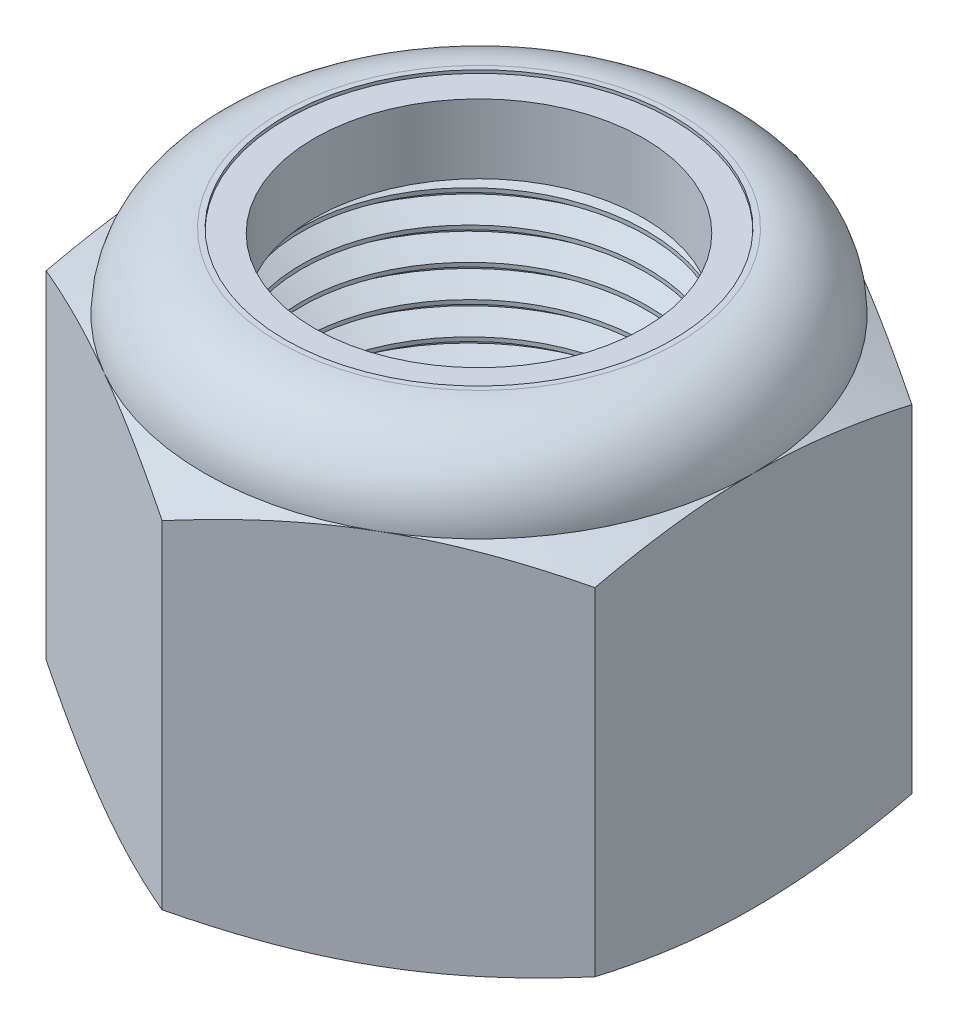
SolidWorks part; units mm, degrees
note: '?' marks a value the reader was unsure of.
ref_plane "Front" through (0, 0, 0) normal (0, 0, 1) x (1, 0, 0)
ref_plane "Top" through (0, 0, 0) normal (0, 1, 0) x (1, 0, 0)
ref_plane "Right" through (0, 0, 0) normal (1, 0, 0) x (0, 0, -1)
sketch "Sketch8" plane through (0, 0, 0) normal (1, 0, 0) x (0, 0, -1)
  line L0 (0, 0) -> (0, 22.225) construction
  line L1 (13.4937, 0) -> (-13.4937, 0) construction
  line L2 (-9.525, 22.225) -> (9.525, 22.225) construction
  line L3 (9.525, 22.225) -> (9.525, 20.6375) construction
sketch "Sketch1" plane through (0, 0, 0) normal (0, 1, 0) x (1, 0, 0)
  line L1 (0, 15.5812) -> (-13.4937, 7.7906)
  line L2 (-13.4937, 7.7906) -> (-13.4937, -7.7906)
  line L3 (-13.4937, -7.7906) -> (0, -15.5812)
  line L4 (0, -15.5812) -> (13.4938, -7.7906)
  line L5 (13.4938, -7.7906) -> (13.4938, 7.7906)
  line L6 (13.4938, 7.7906) -> (0, 15.5812)
  circle A0 centre (0, 0) radius 13.4938 construction
  circle A1 centre (0, 0) radius 9.525
extrude "Extrude1" add sketch "Sketch1" along normal up to vertex (22.225 mm away) up to point (0, 22.225, 0)
sketch "Sketch5" plane through (0, 0, 0) normal (1, 0, 0) x (0, 0, -1)
  line L0 (0, 0) -> (13.4937, 0)
  line L1 (13.4937, 0) -> (15.5812, 0.9734)
  line L2 (15.5812, 0.9734) -> (15.5812, 17.5474)
  line L3 (15.5812, 17.5474) -> (13.4937, 18.5208)
  line L4 (9.7896, 22.225) -> (9.7896, 23.495)
  line L5 (9.7896, 23.495) -> (16.8512, 23.495)
  line L6 (16.8512, 23.495) -> (16.8512, -1.27)
  line L7 (16.8512, -1.27) -> (0, -1.27)
  line L8 (0, -1.27) -> (0, 0)
  line L9 (13.4937, 18.5208) -> (13.4937, 0) construction
  line L12 (15.5812, 22.225) -> (15.5812, 0) construction
  line L13 (15.5812, 11.1125) -> (16.8512, 11.1125) construction
  line L15 (0, 0) -> (0, 23.495) construction
  line L18 (13.4937, 0) -> (-13.4937, 0) construction
  line L19 (7.7906, 22.225) -> (15.5812, 22.225) construction
  line L20 (0, 23.495) -> (9.7896, 23.495) construction
  line L21 (7.7906, 0) -> (15.5812, 0) construction
  arc A0 (13.4937, 18.5208) -> (9.7896, 22.225) centre (9.7896, 18.5208) ccw
  dimension "D1" = 25
  dimension "D2" = 1.27
  dimension "D4" = 3.7042
revolve "Cut-Revolve3" cut sketch "Sketch5" angle 360 about L15
sketch "Sketch4" plane through (0, 0, 0) normal (1, 0, 0) x (0, 0, -1)
  line L0 (0, 18.5208) -> (10.4775, 18.5208)
  line L1 (10.4775, 18.5208) -> (0, 13.6351)
  line L3 (0, 4.8857) -> (10.4775, 0)
  line L4 (10.4775, 0) -> (0, 0)
  line L5 (0, 0) -> (0, 18.5208) construction
  line L10 (0, 0) -> (0, 22.225) construction
  line L11 (0, 4.8857) -> (0, 0)
  line L12 (0, 18.5208) -> (0, 13.6351)
  line L13 (11.6859, 18.5208) -> (0, 18.5208) construction
  dimension "D1" = 25
  dimension "D2" = 20.955
sketch "Sketch6" plane through (0, 0, 0) normal (1, 0, 0) x (0, 0, -1)
  line L0 (0, 18.5208) -> (13.3414, 18.5208)
  line L1 (9.7896, 22.0726) -> (4.8948, 22.0726)
  line L2 (0, 23.495) -> (0, 18.5208)
  line L3 (4.8948, 23.495) -> (0, 23.495)
  line L4 (0, 23.495) -> (9.7896, 23.495) construction
  line L5 (0, 0) -> (0, 23.495) construction
  line L6 (0, 23.495) -> (0, 0) construction
  line L7 (4.8948, 22.0726) -> (4.8948, 23.495)
  line L8 (9.7896, 22.225) -> (9.7896, 22.0726) construction
  line L9 (4.8948, 22.0726) -> (0, 22.0726) construction
  line L10 (0, 22.0726) -> (0, 13.6351) construction
  arc A0 (13.3414, 18.5208) -> (9.7896, 22.0726) centre (9.7896, 18.5208) ccw
  arc A1 (13.4937, 18.5208) -> (9.7896, 22.225) centre (9.7896, 18.5208) ccw construction
  dimension "D1" = 0.1524
revolve "Cut-Revolve4" cut sketch "Sketch6" angle 360 about L6
revolve "Cut-Revolve2" cut sketch "Sketch4" angle 360 about L5
sketch "Sketch7" plane through (0, 0, 0) normal (1, 0, 0) x (0, 0, -1)
  line L0 (8.0962, 18.597) -> (13.2643, 18.597)
  line L1 (9.7896, 21.9964) -> (8.0962, 21.9964)
  line L2 (8.0962, 21.9964) -> (8.0962, 18.597)
  line L3 (8.0962, 18.597) -> (0, 18.597) construction
  line L4 (0, 18.597) -> (0, 21.9964) construction
  line L5 (0, 21.9964) -> (8.0962, 21.9964) construction
  line L6 (8.0962, 18.597) -> (8.0962, 18.5208) construction
  line L7 (0, 18.5208) -> (13.3414, 18.5208) construction
  line L8 (9.7896, 21.9964) -> (9.7896, 22.0726) construction
  arc A0 (13.2643, 18.597) -> (9.7896, 21.9964) centre (9.7896, 18.5208) ccw
  arc A2 (13.3414, 18.5208) -> (9.7896, 22.0726) centre (9.7896, 18.5208) ccw construction
  dimension "D1" = 0.0762
  dimension "D2" = 16.1925
revolve "Revolve2" add sketch "Sketch7" angle 360 about L4
sketch "Sketch2" plane through (0, 0, 0) normal (1, 0, 0) x (0, 0, -1)
  line L0 (-9.525, 0) -> (-9.525, 18.5208) construction
  line L1 (0, 0) -> (9.525, 0)
  line L2 (0, 0) -> (0, 18.5208)
  line L3 (0, 18.5208) -> (9.525, 18.5208)
  line L4 (9.525, 0) -> (9.525, 18.5208)
  line L6 (11.6859, 18.5208) -> (13.4937, 18.5208) construction
  line L7 (0, -9.525) -> (0, 0) construction
revolve "Revolve1" add sketch "Sketch2" angle 360 about L7
sketch "Sketch9" plane through (0, 0, 0) normal (1, 0, 0) x (0, 0, -1)
  line L0 (9.6969, 20.0091) -> (9.6969, 18.4216) construction
  line L1 (9.6969, 18.4216) -> (8.322, 19.2154) construction
  line L2 (8.322, 19.2154) -> (9.6969, 20.0091) construction
  line L3 (8.4939, 19.3146) -> (8.4939, 19.1161) construction
  line L4 (9.525, 19.9099) -> (9.525, 18.5208) construction
  line L5 (8.322, 19.2154) -> (8.4939, 19.2154) construction
  line L6 (9.525, 19.2154) -> (9.6969, 19.2154) construction
  line L7 (9.6109, 19.2154) -> (9.6109, 19.9595) construction
  line L8 (9.6969, 18.4216) -> (9.6109, 19.9595)
  line L9 (9.6109, 19.9595) -> (8.4939, 19.3146)
  line L10 (8.4939, 19.3146) -> (8.4939, 19.1161)
  line L11 (8.4939, 19.1161) -> (9.6969, 18.4216)
  dimension "D1" = 1.5875
  dimension "D2" = 0.1984
sketch "Sketch10" plane through (0, 18.5208, 0) normal (0, 1, 0) x (1, 0, 0)
  circle A1 centre (0, 0) radius 9.525
  circle A2 centre (0, 0) radius 9.525
  dimension "D1" = 0
curve "Helix/Spiral1" pitch 1.5875 height 23.8125 turns 15
sweep "Cut-Sweep1" cut profiles "Sketch9" path "Helix/Spiral1" align with end faces yes
sketch "Sketch11" plane through (0, 0, 0) normal (1, 0, 0) x (0, 0, -1)
  line L0 (0, 0) -> (0, 22.225) construction
  line L1 (13.4937, 0) -> (-13.4937, 0) construction
  line L4 (0, 22.225) -> (0, 0) construction
  line L5 (0, 11.1125) -> (9.525, 11.1125) construction
  line L6 (0, 0) -> (10.4775, 0)
  line L7 (0, 4.8857) -> (0, 0)
  line L8 (10.4775, 0) -> (0, 4.8857)
  dimension "D1" = 20.955
  dimension "D2" = 25
revolve "Revolve3" add sketch "Sketch11" angle 360 about L4
sketch "Sketch12" plane through (0, 0, 0) normal (1, 0, 0) x (0, 0, -1)
  line L0 (10.4775, 18.5208) -> (0, 18.5208)
  line L1 (0, 18.5208) -> (0, 0)
  line L2 (0, 0) -> (10.4775, 0)
  line L3 (13.4937, 0) -> (-13.4937, 0) construction
  line L4 (10.4775, 0) -> (10.4775, 18.5208)
  line L5 (-10.4775, 0) -> (10.4775, 0) construction
revolve "Revolve4" add sketch "Sketch12" angle 360 about L0
combine bodies "Combine1" operation type subtract main body 136 bodies to subtract 133
ref_plane "Contact Plane 1" through (0, 0, 0) normal (0, -1, 0) x (1, 0, 0)
ref_axis "Center Axis 1" through (0, -2.1015, 0) along (0, 1, 0)?
equation "\"D4@Sketch5\"=\"Height@Sketch8\"/6"
equation "\"D1@Sketch9\"=\"Thread Pitch@Sketch8\""
equation "\"D2@Sketch9\"=\"Thread Pitch@Sketch8\"/8"
equation "\"D4@Helix/Spiral1\"=\"Thread Pitch@Sketch8\""
equation "\"D3@Helix/Spiral1\"=\"Thread Pitch@Sketch8\"+\"Height@Sketch8\""
equation "\"D2@Sketch4\"=\"Thread Dia@Sketch8\"*1.1"
equation "\"D1@Sketch11\"=\"Thread Dia@Sketch8\"*1.1"
equation "\"D2@Sketch7\"=\"Thread Dia@Sketch8\"*.85"
